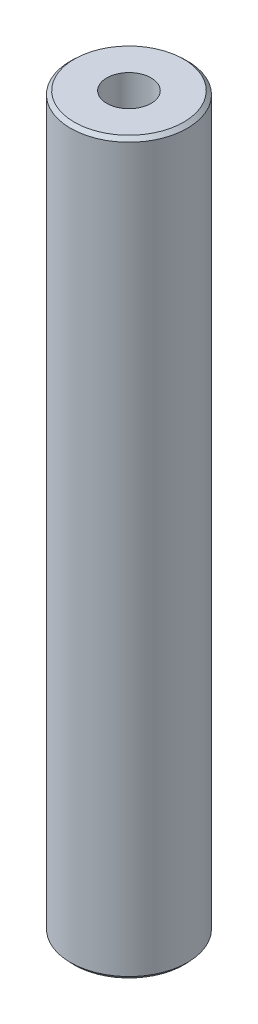
SolidWorks part; units mm, degrees
ref_plane "Front Plane" through (0, 0, 0) normal (0, 0, 1) x (1, 0, 0)
ref_plane "Top Plane" through (0, 0, 0) normal (0, 1, 0) x (1, 0, 0)
ref_plane "Right Plane" through (0, 0, 0) normal (1, 0, 0) x (0, 0, -1)
sketch "Sketch1" plane through (0, 0, 0) normal (0, 1, 0) x (1, 0, 0)
  circle A0 centre (0, 0) radius 47.5
  dimension "SHAFT_OD" = 95
extrude "Boss-Extrude1" add sketch "Sketch1" along normal blind 593.6644
sketch "Sketch2" plane through (0, 0, 0) normal (0, 1, 0) x (1, 0, 0)
  circle A0 centre (0, 0) radius 18.0274
  dimension "BORE_D" = 36.0548
extrude "Cut-Extrude1" cut sketch "Sketch2" along normal through all
chamfer "Chamfer1" distance 2.8064 angle 47.08 2 edges at (0, 593.6644, 47.5) (0, 0, 47.5) first distance on face at (0, 593.6644, 47.5) first distance on face at (0, 0, 18.0274)
